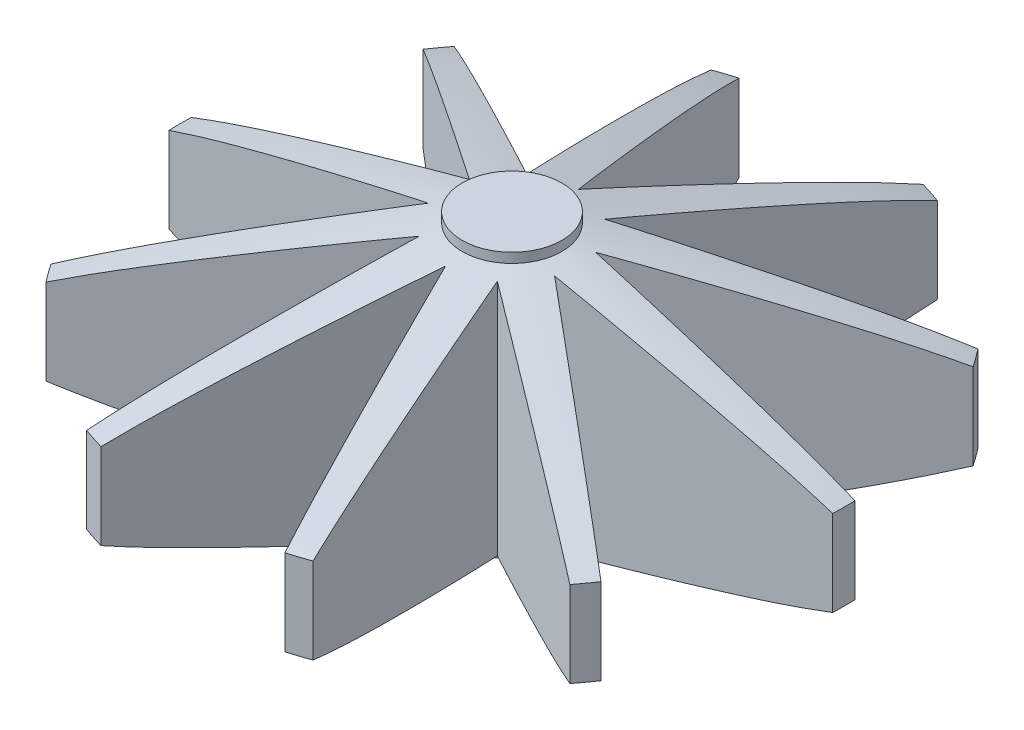
SolidWorks part; units mm, degrees
ref_plane "Front Plane" through (0, 0, 0) normal (0, 0, 1) x (1, 0, 0)
ref_plane "Top Plane" through (0, 0, 0) normal (0, 1, 0) x (1, 0, 0)
ref_plane "Right Plane" through (0, 0, 0) normal (1, 0, 0) x (0, 0, -1)
sketch "Sketch2" plane through (0, 0, 0) normal (0, 0, 1) x (1, 0, 0)
  line L0 (0, 0) -> (9.525, 0)
  line L1 (9.525, 0) -> (9.525, 14.5536)
  line L2 (0, 0) -> (0, 16.6813)
  line L3 (0, 67.4813) -> (0, 76.2)
  line L4 (0, 76.2) -> (9.525, 76.2)
  line L5 (9.525, 76.2) -> (9.525, 61.6464)
  line L6 (0, 67.4813) -> (0, 16.6813)
  line L7 (9.525, 61.6464) -> (9.525, 14.5536) construction
  line L8 (0, 38.1) -> (76.2, 38.1) construction
  line L9 (76.2, 38.1) -> (101.6, 38.1) construction
  arc A0 (9.525, 14.5536) -> (9.525, 61.6464) centre (0, 38.1) ccw construction
  conic Q0 (9.525, 61.6464) -> (9.525, 14.5536) control (101.6, 38.1) rho 0.724138
  dimension "D1" = 25.4
  dimension "D2" = 9.525
  dimension "D3" = 76.2
  dimension "D4" = 25.4
  dimension "D5" = 76.2
revolve "Revolve1" add sketch "Sketch2" angle 360 about L2
sketch "Sketch3" plane through (0, 0, 0) normal (0, 1, 0) x (1, 0, 0)
  line L0 (-27.7345, -88.9) -> (0, -12.7)
  line L1 (0, -12.7) -> (27.7345, -88.9)
  line L2 (27.7345, -88.9) -> (-27.7345, -88.9)
  line L3 (0, 0) -> (0, -12.7) construction
  line L4 (0, -88.9) -> (0, -12.7) construction
  dimension "D1" = 40
  dimension "D2" = 12.7
  dimension "D3" = 76.2
extrude "Cut-Extrude1" cut sketch "Sketch3" along normal through all
pattern_circular "CirPattern2" count 10 over 360 about axis through (0, 0, 0) along (0, -1, 0) of "Cut-Extrude1"
sketch "Sketch4" plane through (0, 0, 0) normal (0, 0, 1) x (1, 0, 0)
  line L0 (9.525, 63.5) -> (50.8, 63.5)
  line L1 (9.525, 61.6464) -> (9.525, 76.2) construction
  line L2 (63.5, 50.8) -> (63.5, 25.4)
  line L3 (50.8, 12.7) -> (9.525, 12.7)
  line L4 (9.525, 12.7) -> (0, 12.7)
  line L5 (0, 12.7) -> (0, 63.5)
  line L6 (0, 63.5) -> (9.525, 63.5)
  line L7 (0, 60.8324) -> (0, 15.3676) construction
  line L8 (0, 60.8324) -> (0, 15.3676) construction
  line L9 (0, 38.1) -> (21.9378, 38.1) construction
  line L10 (0, 0) -> (0, -12.6299) construction
  line L11 (9.525, 0) -> (9.525, 14.5536) construction
  line L12 (21.9378, 38.1) -> (63.5, 38.1) construction
  arc A0 (50.8, 63.5) -> (63.5, 50.8) centre (50.8, 50.8) cw
  arc A1 (63.5, 25.4) -> (50.8, 12.7) centre (50.8, 25.4) cw
  spline S0 degree 3 poles (0, 60.8324) (0.9597, 60.1545) (1.917, 59.4499) (3.8299, 58.0208) (4.7852, 57.2946) (6.6941, 55.8205) (7.6475, 55.0726) (9.5519, 53.5487) (10.5029, 52.7728) (12.4001, 51.1797) (13.3465, 50.3629) (15.2312, 48.6582) (16.1698, 47.7725) (17.5653, 46.3322) (18.0283, 45.8332) (18.7174, 45.0357) (18.9461, 44.7615) (19.4011, 44.1901) (19.6275, 43.8925) (20.0737, 43.2663) (20.294, 42.9377) (20.7246, 42.2293) (20.9353, 41.8508) (21.2371, 41.2079) (21.335, 40.9812) (21.5195, 40.496) (21.6066, 40.2372) (21.7235, 39.8068) (21.7595, 39.658) (21.824, 39.347) (21.8526, 39.1836) (21.8988, 38.8433) (21.9161, 38.6688) (21.937, 38.3098) (21.9403, 38.1241) (21.9318, 37.7623) (21.9202, 37.5831) (21.8839, 37.2314) (21.8598, 37.064) (21.7742, 36.5811) (21.6988, 36.284) (21.5342, 35.7436) (21.4439, 35.4959) (21.2535, 35.0279) (21.1541, 34.8098) (20.8505, 34.1918) (20.6396, 33.824) (20.2093, 33.1334) (19.9896, 32.8116) (19.5446, 32.1971) (19.3191, 31.9044) (18.8656, 31.341) (18.6377, 31.0703) (17.9511, 30.2821) (17.4898, 29.7878) (16.0999, 28.36) (15.1651, 27.4802) (13.2881, 25.786) (12.3456, 24.9737) (10.4563, 23.3889) (9.5094, 22.6169) (7.6135, 21.1006) (6.6643, 20.3563) (4.764, 18.8892) (3.8129, 18.1663) (1.9085, 16.7439) (0.9555, 16.0425) (0, 15.3676) knots 0 0 0 0 0.0625 0.0625 0.125 0.125 0.1875 0.1875 0.25 0.25 0.3125 0.3125 0.375 0.375 0.40625 0.40625 0.421875 0.421875 0.4375 0.4375 0.453125 0.453125 0.46875 0.46875 0.476563 0.476563 0.484375 0.484375 0.488281 0.488281 0.492188 0.492188 0.496094 0.496094 0.5 0.5 0.503906 0.503906 0.507813 0.507813 0.515625 0.515625 0.523438 0.523438 0.53125 0.53125 0.546875 0.546875 0.5625 0.5625 0.578125 0.578125 0.59375 0.59375 0.625 0.625 0.6875 0.6875 0.75 0.75 0.8125 0.8125 0.875 0.875 0.9375 0.9375 1 1 1 1 construction
  dimension "D4" = 12.7
  dimension "D1" = 50.8
  dimension "D3" = 127
revolve "Revolve2" add sketch "Sketch4" angle 360 about L5
combine bodies "Combine2" operation type common bodies to combine 103 104
